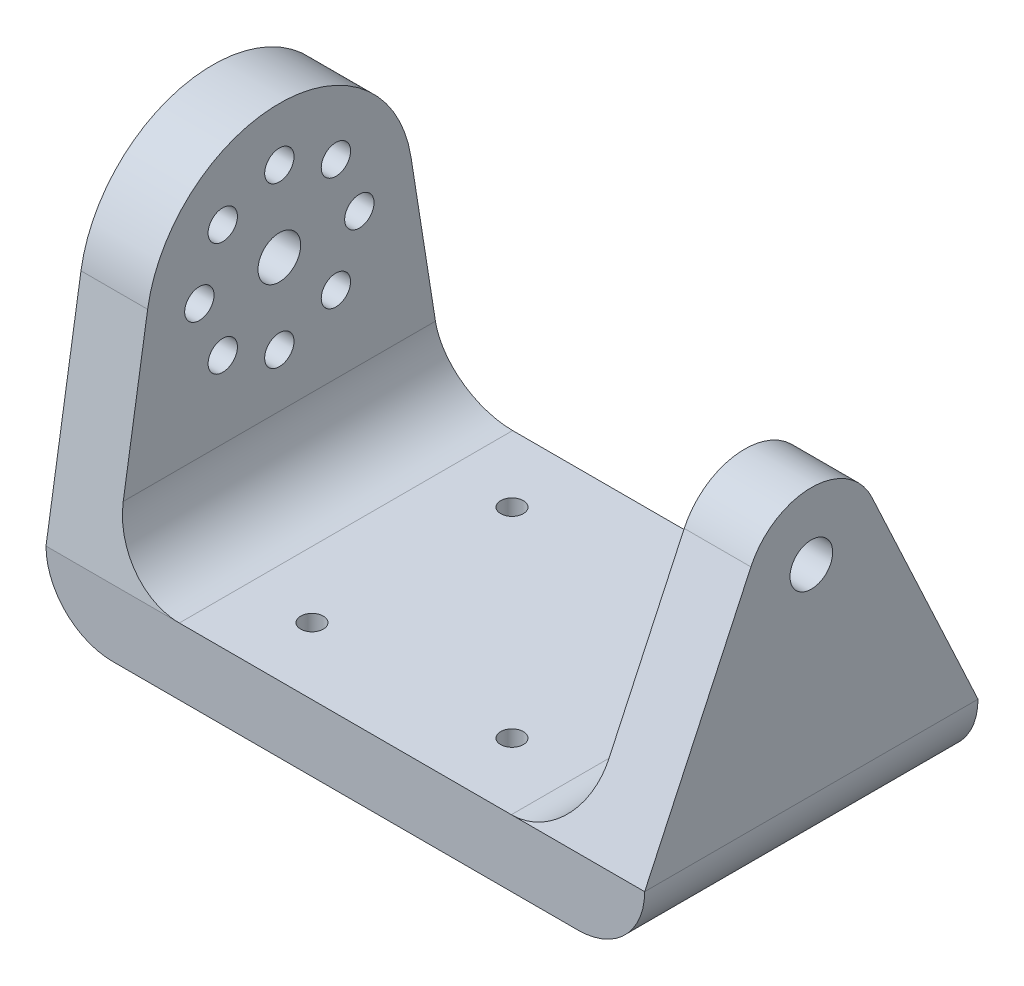
SolidWorks part; units mm, degrees
material "ABS"
ref_plane "正面" through (0, 0, 0) normal (0, 0, 1) x (1, 0, 0)
ref_plane "平面" through (0, 0, 0) normal (0, 1, 0) x (1, 0, 0)
ref_plane "右側面" through (0, 0, 0) normal (1, 0, 0) x (0, 0, -1)
sketch "ｽｹｯﾁ1" plane through (0, 0, 0) normal (0, 1, 0) x (1, 0, 0)
  line L1 (22.45, 0) -> (-22.45, 0)
  line L2 (22.45, 0) -> (22.45, 25)
  line L3 (22.45, 25) -> (-22.45, 25)
  line L4 (-22.45, 0) -> (-22.45, 25)
  dimension "D1" = 44.9
  dimension "D2" = 25
extrude "ﾎﾞｽ - 押し出し1" add sketch "ｽｹｯﾁ1" along normal blind 5
sketch "ｽｹｯﾁ2" plane through (-22.45, 0, 0) normal (-1, 0, 0) x (0, 0, 1)
  line L0 (-25, 5) -> (0, 5)
  line L1 (0, 5) -> (-2.6231, 21.5641)
  line L2 (-22.3769, 21.5641) -> (-25, 5)
  line L3 (-12.5, 5) -> (-12.5, 20) construction
  arc A0 (-2.6231, 21.5641) -> (-22.3769, 21.5641) centre (-12.5, 20) ccw
  circle A1 centre (-12.5, 20) radius 6 construction
  circle A2 centre (-12.5, 26) radius 1.1
  circle A3 centre (-8.2574, 24.2426) radius 1.1
  circle A4 centre (-6.5, 20) radius 1.1
  circle A5 centre (-8.2574, 15.7574) radius 1.1
  circle A6 centre (-12.5, 14) radius 1.1
  circle A7 centre (-16.7426, 15.7574) radius 1.1
  circle A8 centre (-18.5, 20) radius 1.1
  circle A9 centre (-16.7426, 24.2426) radius 1.1
  circle A10 centre (-12.5, 20) radius 1.6
  point P28 (-12.5, 20)
  dimension "D1" = 20
  dimension "D3" = 12
  dimension "D4" = 2.2
  dimension "D6" = 3.2
  dimension "D2" = 15
  dimension "D5" = 8
extrude "ﾎﾞｽ - 押し出し2" add sketch "ｽｹｯﾁ2" against normal blind 5
sketch "ｽｹｯﾁ3" plane through (22.45, 0, 0) normal (1, 0, 0) x (0, 0, -1)
  line L2 (25, 5) -> (0, 5) construction
  line L3 (0, 5) -> (7.9673, 22.1106)
  line L4 (17.0327, 22.1106) -> (25, 5)
  line L5 (25, 5) -> (0, 5)
  arc A1 (17.0327, 22.1106) -> (7.9673, 22.1106) centre (12.5, 20) ccw
  circle A2 centre (12.5, 20) radius 1.6
  circle A3 centre (12.5, 20) radius 1.6 construction
  dimension "D1" = 3.2
  dimension "D2" = 5
extrude "ﾎﾞｽ - 押し出し3" add sketch "ｽｹｯﾁ3" against normal blind 5
fillet "ﾌｨﾚｯﾄ1" radius 5 4 edges at (17.45, 5, -12.5) (-17.45, 5, -12.5) (22.45, 0, -12.5) (-22.45, 0, -12.5)
sketch "ｽｹｯﾁ4" plane through (0, 5, 0) normal (0, 1, 0) x (1, 0, 0)
  line L0 (0, 25) -> (0, 0) construction
  line L1 (12.45, 25) -> (-12.45, 25) construction
  line L2 (-12.45, 0) -> (12.45, 0) construction
  line L3 (-12.45, 12.5) -> (12.45, 12.5) construction
  line L4 (-12.45, 25) -> (-12.45, 0) construction
  line L5 (12.45, 0) -> (12.45, 25) construction
  line L7 (-7.5, 20) -> (7.5, 20) construction
  line L8 (-7.5, 20) -> (-7.5, 5) construction
  line L9 (-7.5, 5) -> (7.5, 5) construction
  line L10 (7.5, 20) -> (7.5, 5) construction
  line L11 (-7.5, 20) -> (7.5, 5) construction
  line L12 (-7.5, 5) -> (7.5, 20) construction
  circle A0 centre (-7.5, 20) radius 0.85
  circle A1 centre (7.5, 20) radius 0.85
  circle A2 centre (7.5, 5) radius 0.85
  circle A3 centre (-7.5, 5) radius 0.85
  point P12 (0, 12.5)
  dimension "D3" = 1.7
  dimension "D1" = 15
  dimension "D2" = 15
extrude "ｶｯﾄ - 押し出し1" cut sketch "ｽｹｯﾁ4" against normal blind 5
